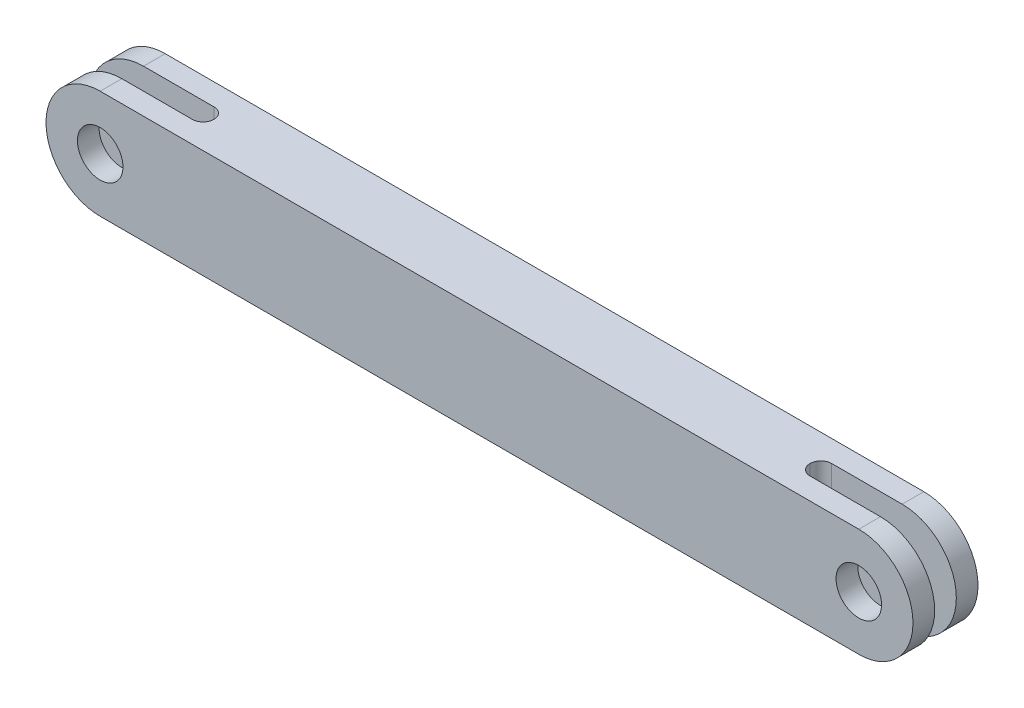
SolidWorks part; units mm, degrees
ref_plane "Front Plane" through (0, 0, 0) normal (0, 0, 1) x (1, 0, 0)
ref_plane "Top Plane" through (0, 0, 0) normal (0, 1, 0) x (1, 0, 0)
ref_plane "Right Plane" through (0, 0, 0) normal (1, 0, 0) x (0, 0, -1)
sketch "Sketch1" plane through (0, 0, 0) normal (0, 0, 1) x (1, 0, 0)
  line L0 (47.7659, 0) -> (-71.679, 0) construction
  line L1 (0, 31.4928) -> (0, -40.7939) construction
  line L2 (35, 5) -> (-35, 5)
  line L3 (-35, -5) -> (35, -5)
  circle A1 centre (-35, 0) radius 5
  circle A5 centre (35, 0) radius 5
  point P9 (0, 0)
  point P10 (0, 0)
  dimension "D1" = 35
  dimension "D3" = 10
extrude "Boss-Extrude1" add sketch "Sketch1" along normal blind 6
sketch "Sketch2" plane through (0, 0, 6) normal (0, 0, 1) x (1, 0, 0)
  line L0 (0, -3.3) -> (0, 3.3) construction
  circle A0 centre (-35, 0) radius 2.1
  circle A1 centre (35, 0) radius 2.1
  dimension "D1" = 4.2
extrude "Cut-Extrude1" cut sketch "Sketch2" against normal through all
sketch "Sketch3" plane through (0, 0, 0) normal (0, 1, 0) x (1, 0, 0)
  line L0 (-40, 0) -> (-40, -6) construction
  line L1 (-52.5, -2) -> (-27.5, -2)
  line L2 (-52.5, -2) -> (-52.5, -4)
  line L3 (-52.5, -4) -> (-27.5, -4)
  line L4 (-27.5, -2) -> (-27.5, -4)
  line L5 (-52.5, -2) -> (-27.5, -4) construction
  line L6 (-52.5, -4) -> (-27.5, -2) construction
  line L7 (0, -3.3) -> (0, 3.3) construction
  line L8 (52.5, -4) -> (27.5, -2) construction
  line L9 (52.5, -2) -> (27.5, -4) construction
  line L10 (27.5, -2) -> (27.5, -4)
  line L11 (52.5, -4) -> (27.5, -4)
  line L12 (52.5, -2) -> (52.5, -4)
  line L13 (52.5, -2) -> (27.5, -2)
  point P0 (-40, -3)
  point P13 (40, -3)
  dimension "D1" = 2
  dimension "D2" = 25
extrude "Cut-Extrude2" cut sketch "Sketch3" against normal blind 10 and the other way blind 10
ref_plane "Mid Front Plane" through (0, 0, 3) normal (0, 0, 1) x (1, 0, 0)
other "SurfaceCut1" flip cut yes
mirror "Mirror12" about plane through (0, 0, 3) normal (0, 0, 1) of bodies 106
fillet "Fillet5" radius 1 8 edges at (27.5, 5, 3) (-27.5, -5, 3) (-27.5, 0, 2) (27.5, 0, 2) (27.5, -5, 3) (-27.5, 5, 3) (27.5, 0, 4) (-27.5, 0, 4)
